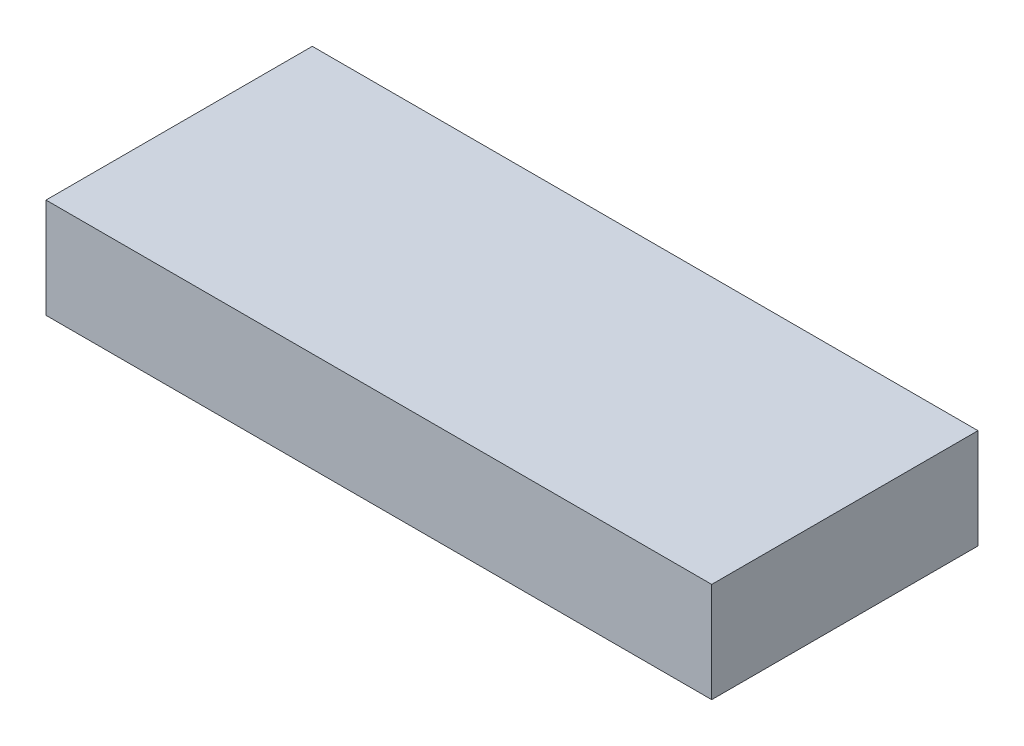
SolidWorks part; units mm, degrees
ref_plane "Front Plane" through (0, 0, 0) normal (0, 0, 1) x (1, 0, 0)
ref_plane "Top Plane" through (0, 0, 0) normal (0, 1, 0) x (1, 0, 0)
ref_plane "Right Plane" through (0, 0, 0) normal (1, 0, 0) x (0, 0, -1)
sketch "Sketch1" plane through (0, 0, 0) normal (0, 1, 0) x (1, 0, 0)
  line L1 (0, 0) -> (-127, 0)
  line L2 (0, 0) -> (0, 50.8)
  line L3 (0, 50.8) -> (-127, 50.8)
  line L4 (-127, 0) -> (-127, 50.8)
  dimension "D1" = 127
  dimension "D2" = 50.8
extrude "Boss-Extrude1" add sketch "Sketch1" along normal blind 19.05
